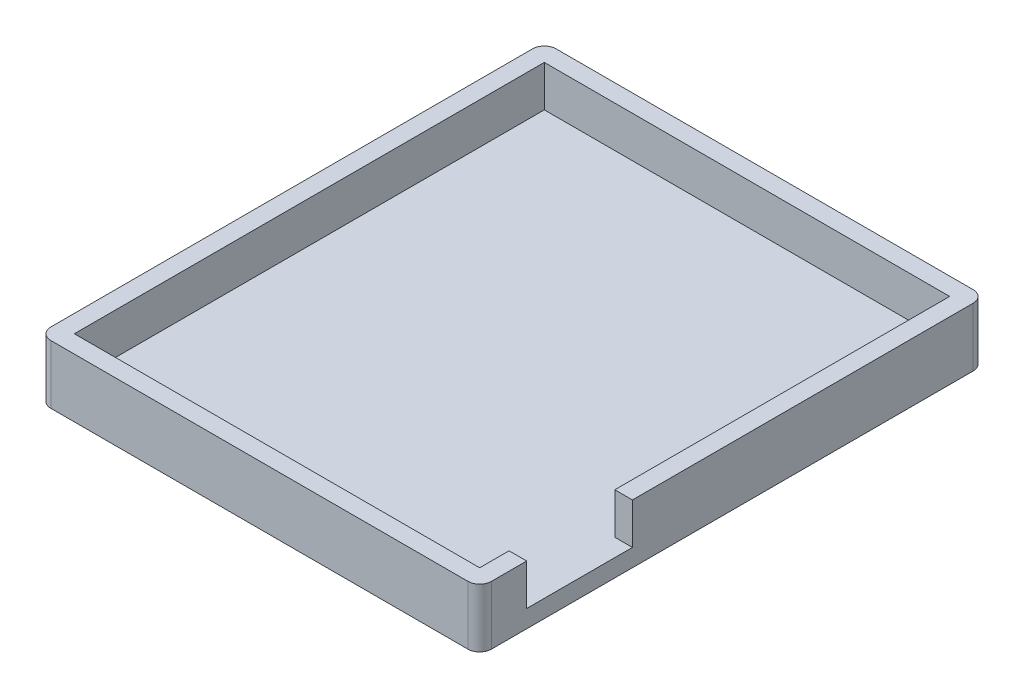
SolidWorks part; units mm, degrees
ref_plane "Front Plane" through (0, 0, 0) normal (0, 0, 1) x (1, 0, 0)
ref_plane "Top Plane" through (0, 0, 0) normal (0, 1, 0) x (1, 0, 0)
ref_plane "Right Plane" through (0, 0, 0) normal (1, 0, 0) x (0, 0, -1)
sketch "Sketch1" plane through (0, 0, 0) normal (0, 1, 0) x (1, 0, 0)
  line L1 (37.5, -43) -> (-37.5, -43)
  line L2 (37.5, -43) -> (37.5, 43)
  line L3 (37.5, 43) -> (-37.5, 43)
  line L4 (-37.5, -43) -> (-37.5, 43)
  line L5 (0, 43) -> (0, -43) construction
  line L6 (37.5, 0) -> (-37.5, 0) construction
  line L7 (34.5, -40) -> (-34.5, -40)
  line L8 (34.5, -40) -> (34.5, 40)
  line L9 (34.5, 40) -> (-34.5, 40)
  line L10 (-34.5, -40) -> (-34.5, 40)
  line L11 (0, 40) -> (0, -40) construction
  line L12 (34.5, 0) -> (-34.5, 0) construction
  point P0 (0, 0)
  point P4 (0, 0)
  dimension "D1" = 75
  dimension "D2" = 86
  dimension "D3" = 80
  dimension "D4" = 69
extrude "Boss-Extrude1" add sketch "Sketch1" along normal blind 3 contours L10 L7 L8 L9 | L4 L1 L2 L3 L7 L10 L9 L8 region at (0, 0, 41.8589) region at (0, 0, 0)
extrude "Boss-Extrude2" add sketch "Sketch1<4>" along normal blind 10
sketch "Sketch1<4>" plane through (0, 0, 0) normal (0, 1, 0) x (1, 0, 0) same geometry as "Sketch1"
sketch "Sketch2" plane through (37.5, 0, 0) normal (1, 0, 0) x (0, 0, -1)
  line L0 (-43, 0) -> (43, 0) construction
  line L1 (-43, 10) -> (-12, 10)
  line L2 (-43, 10) -> (-43, 0)
  line L3 (-43, 0) -> (-12, 0)
  line L4 (-12, 10) -> (-12, 0)
  line L5 (40, 10) -> (40, 3) construction
  line L6 (40, 3) -> (-40, 3) construction
  line L7 (-40, 3) -> (-40, 10) construction
  line L8 (-40, 10) -> (40, 10) construction
  line L9 (43, 0) -> (43, 10) construction
  line L10 (43, 10) -> (-43, 10) construction
  line L11 (-43, 10) -> (-43, 0) construction
  line L12 (40, 10) -> (40, 3)
  line L13 (40, 3) -> (-40, 3)
  line L14 (-40, 3) -> (-40, 10)
  line L15 (-40, 10) -> (40, 10)
  line L16 (-43, 0) -> (43, 0)
  line L17 (43, 0) -> (43, 10)
  line L18 (43, 10) -> (-43, 10)
  line L19 (-43, 10) -> (-43, 0)
  line L20 (-40, 3) -> (-12, 10) construction
  line L22 (-17, 3) -> (-35, 3)
  line L23 (-17, 3) -> (-17, 10)
  line L24 (-17, 10) -> (-35, 10)
  line L25 (-35, 3) -> (-35, 10)
  line L26 (-26, 10) -> (-26, 3) construction
  line L27 (-17, 6.5) -> (-35, 6.5) construction
  point P8 (-26, 6.5)
  dimension "D1" = 28
  dimension "D2" = 18
extrude "Cut-Extrude1" cut sketch "Sketch2" against normal blind 10 contours L25 L13 L23 L18 region at (37.5, 6.5, 26)
fillet "Fillet1" radius 2 4 edges at (-37.5, 5, -43) (37.5, 5, -43) (37.5, 5, 43) (-37.5, 5, 43)
